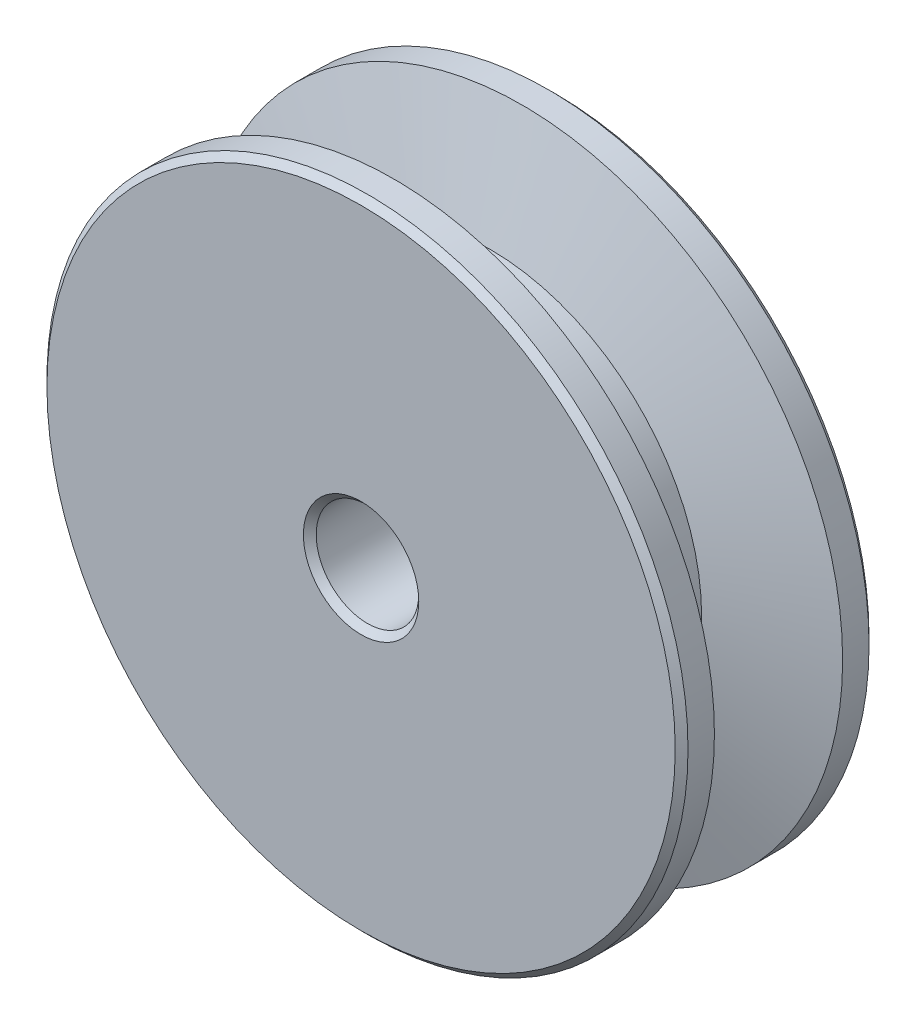
SolidWorks part; units mm, degrees
ref_plane "前视基准面" through (0, 0, 0) normal (0, 0, 1) x (1, 0, 0)
ref_plane "上视基准面" through (0, 0, 0) normal (0, 1, 0) x (1, 0, 0)
ref_plane "右视基准面" through (0, 0, 0) normal (1, 0, 0) x (0, 0, -1)
sketch "草图1" plane through (0, 0, 0) normal (0, 0, 1) x (1, 0, 0)
  circle A0 centre (0, 0) radius 4
  circle A1 centre (0, 0) radius 25
  dimension "D1" = 8
  dimension "D2" = 50
extrude "凸台-拉伸1" add sketch "草图1" along normal blind 7.56 and the other way blind 7.56
sketch "草图3" plane through (0, 0, 0) normal (1, 0, 0) x (0, 0, -1)
  line L0 (0, 25) -> (0, -25) construction
  line L1 (7.56, 25) -> (-7.56, 25) construction
  line L3 (-5, 25) -> (5, 25)
  line L4 (5, 25) -> (2.5, 16.5)
  line L5 (2.5, 16.5) -> (-2.5, 16.5)
  line L6 (-2.5, 16.5) -> (-5, 25)
  line L7 (-7.56, 0) -> (7.56, 0) construction
  line L8 (-7.56, 25) -> (-7.56, -25) construction
  line L9 (7.56, -25) -> (7.56, 25) construction
  dimension "D1" = 8.5
  dimension "D2" = 5
  dimension "D3" = 10
revolve "切除-旋转2" cut sketch "草图3" angle 360 about L7
sketch "草图4" plane through (0, 0, 0) normal (0, 1, 0) x (1, 0, 0)
  circle A0 centre (0, 0) radius 2.1
  dimension "D1" = 4.2
extrude "切除-拉伸1" cut sketch "草图4" along normal through all
sketch "草图5" plane through (0, 0, 0) normal (1, 0, 0) x (0, 0, -1)
  circle A0 centre (0, 0) radius 2.1
  dimension "D1" = 4.2
extrude "切除-拉伸2" cut sketch "草图5" along normal through all
chamfer "倒角1" distance 0.5 angle 45 4 edges at (4, 0, 7.56) (4, 0, -7.56) (25, 0, -7.56) (25, 0, 7.56)
